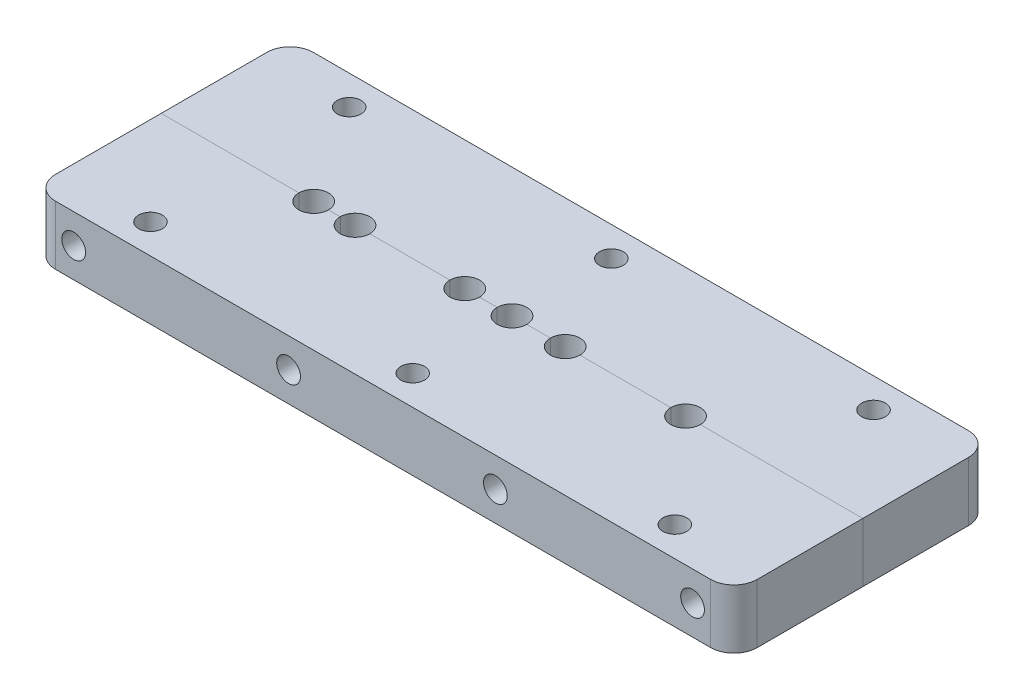
SolidWorks part; units mm, degrees
note: '?' marks a value the reader was unsure of.
material "ABS"
ref_plane "Front Plane" through (0, 0, 0) normal (0, 0, 1) x (1, 0, 0)
ref_plane "Top Plane" through (0, 0, 0) normal (0, 1, 0) x (1, 0, 0)
ref_plane "Right Plane" through (0, 0, 0) normal (1, 0, 0) x (0, 0, -1)
sketch "Sketch1" plane through (0, 0, 0) normal (0, 1, 0) x (1, 0, 0)
  line L1 (-75.4, 27.7) -> (75.4, 27.7)
  line L2 (-75.4, 27.7) -> (-75.4, -27.7)
  line L3 (-75.4, -27.7) -> (75.4, -27.7)
  line L4 (45, 15) -> (-45, 15)
  line L5 (50, -10) -> (50, 10)
  line L6 (-45, -15) -> (45, -15)
  line L7 (-50, 10) -> (-50, -10)
  line L8 (45, 15) -> (-45, 15)
  line L9 (50, -10) -> (50, 10)
  line L10 (-45, -15) -> (45, -15)
  line L11 (-50, 10) -> (-50, -10)
  line L12 (75.4, 27.7) -> (75.4, -27.7)
  line L13 (-75.4, 27.7) -> (75.4, -27.7) construction
  line L14 (-75.4, -27.7) -> (75.4, 27.7) construction
  arc A4 (50, 10) -> (45, 15) centre (45, 10) ccw
  arc A5 (45, -15) -> (50, -10) centre (45, -10) ccw
  arc A6 (-50, -10) -> (-45, -15) centre (-45, -10) ccw
  arc A7 (-45, 15) -> (-50, 10) centre (-45, 10) ccw
  arc A8 (50, 10) -> (45, 15) centre (45, 10) ccw
  arc A9 (45, -15) -> (50, -10) centre (45, -10) ccw
  arc A10 (-50, -10) -> (-45, -15) centre (-45, -10) ccw
  arc A11 (-45, 15) -> (-50, 10) centre (-45, 10) ccw
  point P2 (0, 0)
  dimension "D2" = 12.7
  dimension "D3" = 25.4
  dimension "D1" = 0
extrude "Boss-Extrude1" add sketch "Sketch1" along normal blind 12.7
fillet "Fillet1" radius 5 4 edges at (75.4, 6.35, 27.7) (75.4, 6.35, -27.7) (-75.4, 6.35, -27.7) (-75.4, 6.35, 27.7)
hole_wizard "#10 Clearance Hole1" positions "Sketch2" profile "Sketch3" hole size "#10" standard "ANSI Inch" end condition through all
sketch "Sketch2" plane through (0, 0, 0) normal (0, -1, 0) x (-1, 0, 0)
  point P0 (56.35, 21.35)
  point P3 (0, 21.35)
  point P6 (-56.35, 21.35)
  point P9 (-56.35, -21.35)
  point P12 (0, -21.35)
  point P15 (56.35, -21.35)
sketch "Sketch3" plane through (-56.35, 0, -21.35) normal (1, 0, 0) x (0, 0, -1)
  line L0 (0, 0) -> (0, 12.7)
  line L1 (0, 12.7) -> (2.5527, 12.7)
  line L2 (2.5527, 12.7) -> (2.5527, 0)
  line L5 (2.5527, 0) -> (0, 0)
  line L11 (0, -6.35) -> (0, 107.95) construction
  dimension "Thru Hole Dia." = 5.1054
  dimension "Thru Hole Depth" = 12.7
sketch "Sketch5" plane through (0, 12.7, 0) normal (0, 1, 0) x (1, 0, 0)
  line L0 (-50, 0) -> (50, 0) construction
  line L1 (0, -55) -> (0, 55) construction
  line L4 (-50, 10) -> (-50, -10)
  line L5 (45, 15) -> (-45, 15)
  line L6 (50, -10) -> (50, 10)
  line L7 (-45, -15) -> (45, -15)
  line L8 (-50, 10) -> (-50, -10)
  line L9 (45, 15) -> (-45, 15)
  line L10 (50, -10) -> (50, 10)
  line L11 (-45, -15) -> (45, -15)
  circle A0 centre (-42.6264, 0) radius 3.175
  circle A1 centre (-33.7364, 0) radius 3.175
  circle A2 centre (-10.16, 0) radius 3.175
  arc A4 (-45, 15) -> (-50, 10) centre (-45, 10) ccw
  arc A5 (50, 10) -> (45, 15) centre (45, 10) ccw
  arc A6 (45, -15) -> (50, -10) centre (45, -10) ccw
  arc A7 (-50, -10) -> (-45, -15) centre (-45, -10) ccw
  arc A8 (-45, 15) -> (-50, 10) centre (-45, 10) ccw
  arc A9 (50, 10) -> (45, 15) centre (45, 10) ccw
  arc A10 (45, -15) -> (50, -10) centre (45, -10) ccw
  arc A11 (-50, -10) -> (-45, -15) centre (-45, -10) ccw
  circle A12 centre (0, 0) radius 3.175
  circle A14 centre (37.3, 0) radius 3.175
  circle A15 centre (11.43, 0) radius 3.175
  dimension "D2" = 6.35
  dimension "D3" = 6.35
  dimension "D4" = 6.35
  dimension "D5" = 6.35
  dimension "D7" = 6.35
  dimension "D11" = 6.35
  dimension "D8" = 7.3736
  dimension "D9" = 8.89
  dimension "D10" = 10.16
  dimension "D12" = 12.7
  dimension "D6" = 11.43
  dimension "D1" = 0
extrude "Boss-Extrude2" add sketch "Sketch5" against normal up to surface (12.7 mm away) up to face at (-56.35, 0, -23.9027)
ref_plane "Plane1" [suppressed] through (0, 0, 0) normal (0, -0.7071, 0.7071) x (1, 0, 0)
ref_axis "Axis1" [suppressed] through (82.94, 0, 0) along (-1, 0, 0)?
ref_plane "Plane2" [suppressed] through (0, 0, 0) normal (0, 0.7071, 0.7071) x (-1, 0, 0)
sketch "Sketch6" [suppressed] plane through (75.4, 0, 0) normal (1, 0, 0) x (0, 0, -1)
  line L0 (0, 25.4) -> (0, 12.7)
  line L1 (-22.7, 25.4) -> (22.7, 25.4) construction
  line L2 (0, 13.97) -> (0, -13.97) construction
  line L3 (0, 12.7) -> (-27.7, 12.7)
  line L4 (-27.7, 0) -> (-27.7, 25.4) construction
  dimension "D1" = 12.7
split "Split1" [suppressed] bodies to split 104
sketch "Sketch7" plane through (0, 0, 0) normal (0, -1, 0) x (1, 0, 0)
  line L4 (75.4, -22.7) -> (75.4, 22.7)
  line L9 (75.4, -22.7) -> (75.4, 22.7)
  line L13 (70.4, 27.7) -> (-70.4, 27.7)
  line L14 (70.4, 27.7) -> (-70.4, 27.7)
  line L15 (-75.4, 22.7) -> (-75.4, -22.7)
  line L16 (-75.4, 22.7) -> (-75.4, -22.7)
  line L17 (-70.4, -27.7) -> (70.4, -27.7)
  line L18 (-70.4, -27.7) -> (70.4, -27.7)
  arc A4 (75.4, 22.7) -> (70.4, 27.7) centre (70.4, 22.7) ccw
  arc A10 (75.4, 22.7) -> (70.4, 27.7) centre (70.4, 22.7) ccw
  arc A14 (-70.4, 27.7) -> (-75.4, 22.7) centre (-70.4, 22.7) ccw
  arc A15 (-70.4, 27.7) -> (-75.4, 22.7) centre (-70.4, 22.7) ccw
  arc A26 (-75.4, -22.7) -> (-70.4, -27.7) centre (-70.4, -22.7) ccw
  arc A28 (-75.4, -22.7) -> (-70.4, -27.7) centre (-70.4, -22.7) ccw
  arc A30 (70.4, -27.7) -> (75.4, -22.7) centre (70.4, -22.7) ccw
  arc A31 (70.4, -27.7) -> (75.4, -22.7) centre (70.4, -22.7) ccw
  dimension "D1" = 0
extrude "Boss-Extrude3" [suppressed] add sketch "Sketch7" along normal up to surface (12.7 mm away)
fillet "Fillet2" [suppressed] radius 2.54
hole_wizard "#10 Clearance Hole2" positions "Sketch8" profile "Sketch9" hole size "#10" standard "ANSI Inch" end condition through all
sketch "Sketch8" plane through (0, 0, 27.7) normal (0, 0, 1) x (1, 0, 0)
  line L0 (-75.4, 6.35) -> (75.4, 6.35) construction
  line L1 (-75.4, 0) -> (-75.4, 12.7) construction
  line L2 (75.4, 12.7) -> (75.4, 0) construction
  line L3 (0, -55) -> (0, 55) construction
  point P9 (-66.51, 6.35)
  point P11 (-20.32, 6.35)
  point P13 (24.13, 6.35)
  point P15 (66.51, 6.35)
  dimension "D1" = 8.89
  dimension "D2" = 20.32
  dimension "D3" = 24.13
  dimension "D4" = 8.89
sketch "Sketch9" plane through (66.51, 6.35, 27.7) normal (1, 0, 0) x (0, -1, 0)
  line L0 (0, 0) -> (0, 55.4)
  line L1 (0, 55.4) -> (2.5527, 55.4)
  line L2 (2.5527, 55.4) -> (2.5527, 0)
  line L5 (2.5527, 0) -> (0, 0)
  line L11 (0, -6.35) -> (0, 107.95) construction
  dimension "Thru Hole Dia." = 5.1054
  dimension "Thru Hole Depth" = 55.4
fillet "Fillet4" [suppressed] radius 3.175
fillet "Fillet5" [suppressed] radius 3.175
ref_plane "Plane3" [suppressed] through (0, 12.7, 12.7) normal (0, 0.7071, 0.7071) x (1, 0, 0)
ref_plane "Plane4" [suppressed] through (0, 21.6803, 21.6803) normal (0, 0.7071, 0.7071) x (1, 0, 0)
hole_wizard "CBORE for #10 Binding Head Machine Screw1" [suppressed] positions "Sketch12" profile "Sketch13" counterbore size "#10" standard "ANSI Inch"
sketch "Sketch12" [suppressed] plane through (0, 21.6803, 21.6803) normal (0, 0.7071, 0.7071) x (1, 0, 0)
  line L0 (-75.4, 17.9605) -> (-45.8014, 17.9605) construction
  line L1 (-75.4, 17.9605) -> (-75.4, 1.9092) construction
  point P7 (-56.35, 11.6105)
  dimension "D1" = 6.35
  dimension "D2" = 19.05
sketch "Sketch13" plane through (-56.35, 29.8901, 13.4704) normal (1, 0, 0) x (0, -0.7071, 0.7071)
  line L0 (0, 0) -> (0, 39.5957)
  line L1 (0, 39.5957) -> (2.4892, 38.1)
  line L2 (2.4892, 38.1) -> (2.4892, 9.4742)
  line L3 (2.4892, 9.4742) -> (5.5562, 9.4742)
  line L4 (5.5562, 9.4742) -> (5.5562, 0)
  line L5 (5.5562, 0) -> (0, 0)
  line L10 (0, 39.5957) -> (-2.4892, 38.1) construction
  line L11 (0, -6.35) -> (0, 107.95) construction
  dimension "Hole Dia." = 4.9784
  dimension "Hole Depth" = 38.1
  dimension "C'Bore Dia." = 11.1125
  dimension "C'Bore Depth" = 9.4742
  dimension "Drill Angle" = 118
ref_plane "Plane5" [suppressed] through (-56.35, 0, 0) normal (1, 0, 0) x (0, 0, -1)
ref_plane "Plane6" [suppressed] through (0, 3.7197, 3.7197) normal (0, 0.7071, 0.7071) x (1, 0, 0)
sketch "Sketch15" [suppressed] plane through (0, 3.7197, 3.7197) normal (0, 0.7071, 0.7071) x (1, 0, 0)
  circle A0 centre (-56.35, 11.6105) radius 9.525
  dimension "D1" = 19.05
extrude "Cut-Extrude2" [suppressed] cut sketch "Sketch15" against normal blind 6.35
sketch "Sketch17" [suppressed] plane through (-56.35, 0, 0) normal (1, 0, 0) x (0, 0, -1)
  line L0 (-6.7711, 23.1909) -> (4.4901, 11.9296) construction
  line L1 (-5.011, 24.951) -> (-8.5312, 21.4307) construction
  line L2 (7.7914, 15.2309) -> (-15.2309, -7.7914) construction
  line L4 (11.2253, 18.6648) -> (15.7154, 14.1747)
  line L5 (15.7154, 14.1747) -> (2.2451, 0.7043)
  line L6 (2.2451, 0.7043) -> (-2.2451, 5.1944)
  line L8 (11.2253, 18.6648) -> (-2.2451, 5.1944)
  dimension "D1" = 6.35
  dimension "D2" = 19.05
extrude "Cut-Extrude3" [suppressed] cut sketch "Sketch17" against normal through all
mirror "Mirror1" [suppressed] about plane through (0, 0, 0) normal (1, 0, 0)
split "Split2" trim tools "Front Plane" bodies to split 108 resulting bodies 120 121
equation "\"cable_1_d\"= 0.25"
equation "\"cable_2_d\"= 0.25"
equation "\"cable_3_d\"= 0.25"
equation "\"cable_4_d\"= 0.25"
equation "\"cable_5_d\"= 0.25"
equation "\"cable_6_d\"= 0.25"
equation "\"D2@Sketch5\"=\"cable_1_d\""
equation "\"D3@Sketch5\"=\"cable_2_d\""
equation "\"D4@Sketch5\"=\"cable_3_d\""
equation "\"D5@Sketch5\"=\"cable_4_d\""
equation "\"D7@Sketch5\"=\"cable_6_d\""
equation "\"D11@Sketch5\"=\"cable_5_d\""
